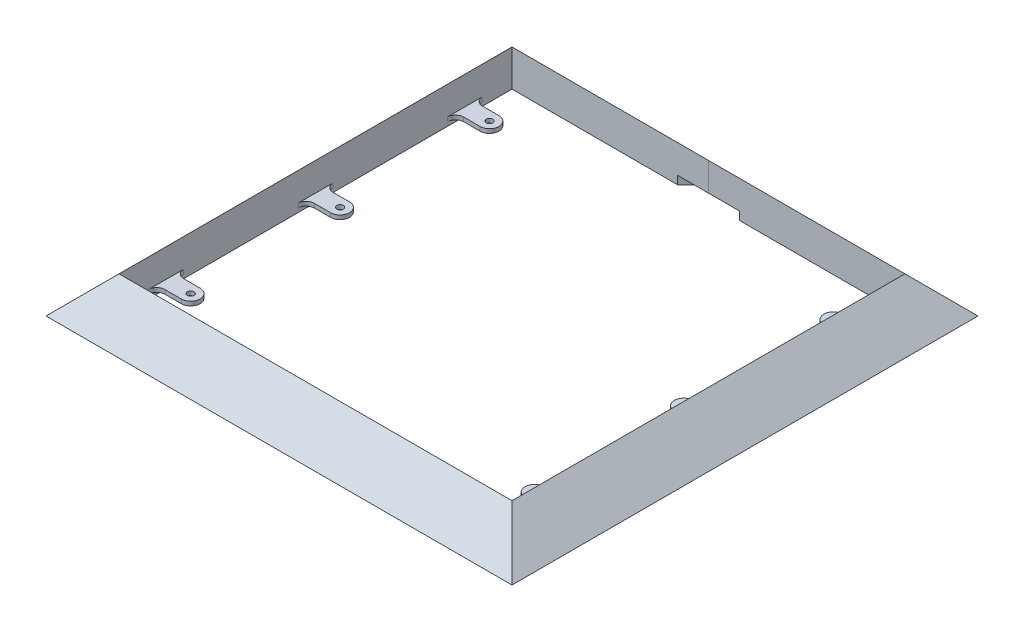
SolidWorks part; units mm, degrees
note: The reader was unsure of these and kept them because the rebuilt part matched: shared geometry of "Sketch1<3>", "Sketch1<6>".
ref_plane "Front Plane" through (0, 0, 0) normal (0, 0, 1) x (1, 0, 0)
ref_plane "Top Plane" through (0, 0, 0) normal (0, 1, 0) x (1, 0, 0)
ref_plane "Right Plane" through (0, 0, 0) normal (1, 0, 0) x (0, 0, -1)
sketch "Sketch1" plane through (0, 0, 0) normal (0, 1, 0) x (1, 0, 0)
  line L0 (0, 0) -> (-1.1174, 2.6977) construction
  line L1 (-1.1174, -2.6977) -> (1.1174, -2.6977) construction
  line L2 (-1.1174, -2.6977) -> (-1.1174, 2.6977) construction
  line L3 (-1.1174, 2.6977) -> (1.1174, 2.6977) construction
  line L4 (1.1174, -2.6977) -> (1.1174, 2.6977) construction
  line L5 (-1.1174, -2.6977) -> (1.1174, 2.6977) construction
  line L6 (-1.1174, 2.6977) -> (1.1174, -2.6977) construction
  line L7 (0, 0) -> (1.1174, 2.6977) construction
  circle A0 centre (0, 0) radius 4.7
  circle A1 centre (-1.1174, 2.6977) radius 0.915
  circle A2 centre (1.1174, 2.6977) radius 0.915
  circle A3 centre (2.6977, 1.1174) radius 0.915 [skipped]
  circle A4 centre (2.6977, -1.1174) radius 0.915 [skipped]
  circle A5 centre (1.1174, -2.6977) radius 0.915
  circle A6 centre (-1.1174, -2.6977) radius 0.915
  circle A7 centre (7.4, -2.3) radius 1.5 construction
  circle A8 centre (8.9, -2.3) radius 0.75
  circle A9 centre (5.9, -2.3) radius 0.75
  circle A10 centre (7.4, -2.3) radius 2.625
  circle A11 centre (-7.4, -2.3) radius 2.625
  point P8 (7.4, -2.3)
  dimension "D3" = 9.4
  dimension "D4" = 1.83
  dimension "D9" = 3
  dimension "D10" = 1.5
  dimension "D11" = 5.25
  dimension "D1" = 45
  dimension "D2" = 5.84
  dimension "D6" = 45
  dimension "D7" = 7.4
  dimension "D8" = 2.3
  dimension "D12" = 7.4
  dimension "D13" = 2.3
  dimension "D5" = 6
extrude "Boss-Extrude1" add sketch "Sketch1" along normal blind 4.37 contours A1 | A6 | A2 | A5
extrude "Boss-Extrude2" add sketch "Sketch1<3>" along normal blind 15 from surface at 4.37 contours A1 | A2 | A5 | A6 | A0 A6 A5 A2 A1 starting at face at (-1.1174, 4.37, -1.7827)
sketch "Sketch1<3>" plane through (0, 0, 0) normal (0, 1, 0) x (1, 0, 0) same geometry as "Sketch1"
sketch "Sketch2" plane through (0, 0, 0) normal (1, 0, 0) x (0, 0, -1)
  line L1 (-5.7, -4) -> (-5.7, 13.85)
  line L2 (-5.7, 13.85) -> (12.15, -4)
  line L5 (-5.7, -4) -> (12.15, -4)
  point P0 (-5.7, -3.8598)
  point P6 (0, 0)
  point P7 (12.2829, -4.1329)
  dimension "D1" = 13.85
  dimension "D2" = 4
  dimension "D3" = 45
  dimension "D4" = 5.7
sketch "Sketch3" plane through (0, 0, 0) normal (0, 1, 0) x (1, 0, 0)
  line L0 (-15.05, -5.7) -> (15.05, -5.7)
  line L2 (-4.35, 5) -> (4.35, 5)
  line L4 (4.35, 5) -> (15.05, -5.7)
  line L5 (0, 0) -> (0, -5.7) construction
  line L6 (-4.35, 5) -> (-15.05, -5.7)
  point P2 (0, -8.3135)
  point P13 (0, 5)
  dimension "D1" = 135
  dimension "D2" = 10.7
  dimension "D3" = 15.05
sketch "Sketch4" plane through (0, 0, 0) normal (0, 1, 0) x (1, 0, 0)
  line L1 (-96, -197.7) -> (96, -197.7)
  line L2 (-96, -197.7) -> (-96, -5.7)
  line L3 (-96, -5.7) -> (96, -5.7)
  line L4 (96, -197.7) -> (96, -5.7)
  line L5 (-96, -197.7) -> (96, -5.7) construction
  line L6 (-96, -5.7) -> (96, -197.7) construction
  point P0 (0, -101.7)
  point P6 (0, -5.7)
  point P16 (-83.1672, -97.1)
  point P21 (-79.4, -101.7)
  dimension "D1" = 192
sweep "Sweep1" add profiles "Sketch2" path "Sketch4"
combine bodies "Combine2" operation type subtract main body 111 bodies to subtract 105
extrude "Cut-Extrude1" cut sketch "Sketch3" against normal through all
extrude "Cut-Extrude4" cut sketch "Sketch1<6>" along normal through all contours A11 | A10 A8 A9 | A9 | A8
sketch "Sketch1<6>" plane through (0, 0, 0) normal (0, 1, 0) x (1, 0, 0) same geometry as "Sketch1"
sketch "Sketch5" plane through (0, 0, 0) normal (0, 1, 0) x (1, 0, 0)
  line L0 (-96, -101.7) -> (-84, -101.7) construction
  line L1 (-84, -97.1) -> (-92, -97.1)
  line L2 (-84, -101.7) -> (-79.4, -101.7) construction
  line L3 (-84, -106.3) -> (-92, -106.3)
  line L8 (-96, -197.7) -> (96, -197.7)
  line L9 (96, -197.7) -> (96, -5.7)
  line L10 (96, -5.7) -> (-96, -5.7)
  line L11 (-96, -5.7) -> (-96, -197.7)
  line L12 (-96, -197.7) -> (96, -197.7)
  line L13 (96, -197.7) -> (96, -5.7)
  line L14 (96, -5.7) -> (-96, -5.7)
  line L15 (-96, -5.7) -> (-96, -197.7)
  circle A0 centre (-84, -101.7) radius 1.6
  arc A1 (-84, -106.3) -> (-84, -97.1) centre (-84, -101.7) ccw
  arc A2 (-92, -97.1) -> (-96, -93.1) centre (-92, -93.1) cw
  arc A3 (-92, -106.3) -> (-96, -110.3) centre (-92, -110.3) ccw
  point P0 (-82.4, -101.7)
  point P15 (-96, -101.7)
  point P18 (-96, -93.1)
  point P19 (-96, -93.8024)
  dimension "D1" = 3.2
  dimension "D2" = 4
  dimension "D3" = 12
  dimension "D4" = 3
  dimension "D5" = 0
extrude "Boss-Extrude4" add sketch "Sketch5" against normal blind 2 contours A3 L3 A1 L1 A2 L15 A0
pattern_linear "LPattern1" count 2 spacing 73 along (0, 0, -1) count 2 spacing 73 along (0, 0, 1) of "Boss-Extrude4"
mirror "Mirror1" about plane through (0, 0, 0) normal (1, 0, 0) of "LPattern1", "Boss-Extrude4"
